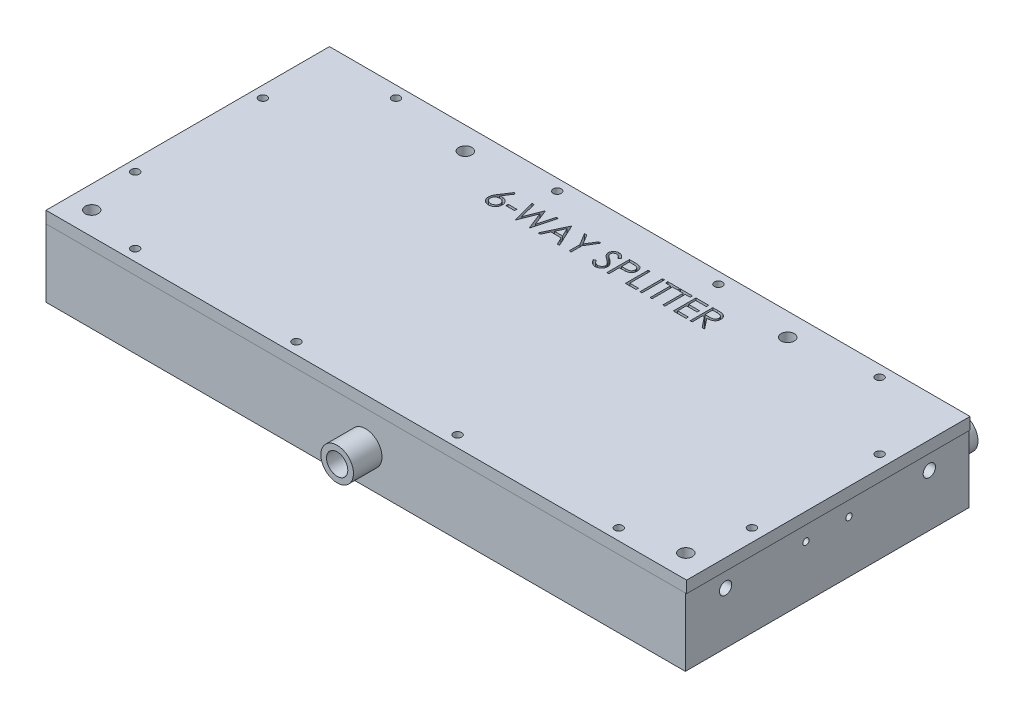
SolidWorks part; units mm, degrees
ref_plane "Front" through (0, 0, 0) normal (0, 0, 1) x (1, 0, 0)
ref_plane "Top" through (0, 0, 0) normal (0, 1, 0) x (1, 0, 0)
ref_plane "Right" through (0, 0, 0) normal (1, 0, 0) x (0, 0, -1)
sketch "Sketch1" plane through (0, 0, 0) normal (0, 1, 0) x (1, 0, 0)
  line L1 (0, 0) -> (179.324, 0)
  line L2 (0, 0) -> (0, 79.502)
  line L3 (0, 79.502) -> (179.324, 79.502)
  line L4 (179.324, 0) -> (179.324, 79.502)
  dimension "D1" = 79.502
  dimension "D2" = 179.324
extrude "Extrude-Thin1" add sketch "Sketch1" along normal blind 19.05 thin thin type one direction reverse wall 6.35
sketch "Sketch10" plane through (0, 0, 0) normal (0, -1, 0) x (1, 0, 0)
  line L0 (0, 0) -> (0, -79.502)
  line L1 (0, 0) -> (179.324, 0)
  line L2 (0, -79.502) -> (179.324, -79.502)
  line L3 (179.324, 0) -> (179.324, -79.502)
  line L4 (163.4056, -15.457) -> (144.9314, -15.457) construction
  line L5 (163.4056, -23.0271) -> (144.9314, -23.0271)
  line L6 (163.4056, -7.8869) -> (144.9314, -7.8869)
  line L7 (123.2539, -15.457) -> (56.0701, -15.457) construction
  line L8 (123.2539, -23.0271) -> (56.0701, -23.0271)
  line L9 (123.2539, -7.8869) -> (56.0701, -7.8869)
  line L10 (89.662, 0) -> (89.662, -15.457) construction
  line L11 (179.324, 0) -> (179.324, -79.502) construction
  line L12 (33.8656, -15.457) -> (15.3914, -15.457) construction
  line L13 (33.8656, -23.0271) -> (15.3914, -23.0271)
  line L14 (33.8656, -7.8869) -> (15.3914, -7.8869)
  arc A0 (163.4056, -23.0271) -> (163.4056, -7.8869) centre (163.4056, -15.457) ccw
  arc A1 (144.9314, -7.8869) -> (144.9314, -23.0271) centre (144.9314, -15.457) ccw
  arc A2 (123.2539, -23.0271) -> (123.2539, -7.8869) centre (123.2539, -15.457) ccw
  arc A3 (56.0701, -7.8869) -> (56.0701, -23.0271) centre (56.0701, -15.457) ccw
  arc A4 (33.8656, -23.0271) -> (33.8656, -7.8869) centre (33.8656, -15.457) ccw
  arc A5 (15.3914, -7.8869) -> (15.3914, -23.0271) centre (15.3914, -15.457) ccw
  point P8 (154.1685, -15.457)
  point P15 (89.662, -15.457)
  point P29 (24.6285, -15.457)
extrude "Boss-Extrude1" add sketch "Sketch10" against normal blind 5.715
sketch "Sketch11" plane through (0, 19.05, 0) normal (0, 1, 0) x (1, 0, 0)
  line L0 (0, 0) -> (0, 79.502)
  line L1 (0, 0) -> (179.6701, 0)
  line L2 (0, 79.502) -> (179.6701, 79.502)
  line L3 (179.6701, 0) -> (179.6701, 79.502)
extrude "Boss-Extrude2" add sketch "Sketch11" along normal blind 3.302 separate body
hole_wizard "#6 Clearance Hole1" positions "Sketch2" profile "Sketch3" hole size "#6" standard "ANSI Inch" end condition through all
sketch "Sketch2" plane through (0, 22.352, 0) normal (0, 1, 0) x (1, 0, 0)
  line L0 (0, 79.502) -> (0, 0) construction
  line L1 (179.324, 79.502) -> (0, 79.502) construction
  line L3 (44.45, 73.152) -> (134.874, 73.152) construction
  line L5 (6.35, 6.477) -> (172.974, 6.477) construction
  point P0 (44.45, 73.152)
  point P2 (134.874, 73.152)
  point P4 (172.974, 6.477)
  point P6 (6.35, 6.477)
  dimension "D1" = 44.45
  dimension "D2" = 6.35
  dimension "D3" = 134.874
  dimension "D4" = 172.974
  dimension "D5" = 6.35
  dimension "D6" = 73.025
sketch "Sketch3" plane through (44.45, 22.352, -73.152) normal (1, 0, 0) x (0, 0, 1)
  line L0 (0, 0) -> (0, 22.352)
  line L1 (0, 22.352) -> (1.8288, 22.352)
  line L2 (1.8288, 22.352) -> (1.8288, 0)
  line L5 (1.8288, 0) -> (0, 0)
  line L11 (0, -6.35) -> (0, 107.95) construction
  dimension "Thru Hole Dia." = 3.6576
  dimension "Thru Hole Depth" = 22.352
sketch "Sketch4" plane through (0, 0, 0) normal (0, 0, 1) x (1, 0, 0)
  line L0 (89.662, 19.05) -> (89.662, 9.525) construction
  line L1 (0, 19.05) -> (179.324, 19.05) construction
  line L2 (89.662, 9.525) -> (0, 9.525) construction
  line L3 (0, 19.05) -> (0, 0) construction
  circle A0 centre (89.662, 9.525) radius 4.572
  dimension "D1" = 9.144
extrude "Extrude-Thin2" add sketch "Sketch4" along normal blind 8.001 thin thin type one direction reverse wall 1.5875
sketch "Sketch5" plane through (0, 0, -79.502) normal (0, 0, -1) x (-1, 0, 0)
  line L0 (-89.662, 19.05) -> (-89.662, 9.525) construction
  line L1 (-179.324, 19.05) -> (0, 19.05) construction
  line L2 (-179.324, 9.525) -> (0, 9.525) construction
  line L3 (0, 19.05) -> (0, 0) construction
  line L4 (-10, 9.525) -> (-32.606, 9.525) construction
  line L6 (-169.324, 9.525) -> (-146.718, 9.525) construction
  circle A0 centre (-10, 9.525) radius 4.572
  circle A1 centre (-32.606, 9.525) radius 4.572
  circle A2 centre (-55.212, 9.525) radius 4.572
  circle A3 centre (-124.112, 9.525) radius 4.572
  circle A7 centre (-146.718, 9.525) radius 4.572
  circle A8 centre (-169.324, 9.525) radius 4.572
  dimension "D1" = 9.144
  dimension "D3" = 22.606
  dimension "D4" = 10
  dimension "D2" = 3
extrude "Extrude-Thin3" add sketch "Sketch5" along normal blind 8.001 thin thin type one direction reverse wall 1.5875
hole_wizard "#4-40 Tapped Hole1" positions "Sketch6" profile "Sketch7" tap size "#4-40" standard "ANSI Inch" end condition through all
sketch "Sketch6" plane through (0, 22.352, 0) normal (0, 1, 0) x (1, 0, 0)
  line L0 (0, 79.502) -> (0, 0) construction
  line L1 (21.844, 3.175) -> (67.056, 3.175) construction
  line L2 (67.056, 3.175) -> (112.268, 3.175) construction
  line L3 (112.268, 3.175) -> (157.48, 3.175) construction
  line L4 (157.48, 3.175) -> (157.48, 76.327) construction
  line L5 (157.48, 76.327) -> (112.268, 76.327) construction
  line L6 (112.268, 76.327) -> (67.056, 76.327) construction
  line L7 (67.056, 76.327) -> (21.844, 76.327) construction
  line L8 (21.844, 76.327) -> (21.844, 3.175) construction
  line L10 (0, 0) -> (179.324, 0) construction
  line L11 (179.324, 79.502) -> (0, 79.502) construction
  line L12 (112.268, 3.175) -> (112.268, 76.327) construction
  line L14 (67.056, 3.175) -> (67.056, 76.327) construction
  line L16 (176.149, 21.844) -> (176.149, 57.658) construction
  line L18 (176.149, 57.658) -> (3.175, 57.658) construction
  line L19 (3.175, 57.658) -> (3.175, 21.844) construction
  line L20 (3.175, 21.844) -> (176.149, 21.844) construction
  line L26 (179.324, 0) -> (179.324, 79.502) construction
  line L27 (44.45, 76.327) -> (44.45, 73.152) construction
  point P0 (157.48, 76.327)
  point P2 (112.268, 76.327)
  point P4 (67.056, 76.327)
  point P6 (21.844, 76.327)
  point P8 (21.844, 3.175)
  point P10 (67.056, 3.175)
  point P12 (112.268, 3.175)
  point P14 (157.48, 3.175)
  point P16 (176.149, 21.844)
  point P18 (176.149, 57.658)
  point P20 (3.175, 57.658)
  point P22 (3.175, 21.844)
  point P62 (89.662, 3.175)
  point P78 (3.175, 39.751)
  dimension "D1" = 21.844
  dimension "D2" = 3.175
  dimension "D3" = 3.175
  dimension "D4" = 89.662
  dimension "D5" = 39.751
  dimension "D6" = 21.844
  dimension "D7" = 3.175
  dimension "D8" = 3.175
sketch "Sketch7" plane through (157.48, 22.352, -76.327) normal (1, 0, 0) x (0, 0, 1)
  line L0 (0, 0) -> (0, 22.352)
  line L1 (0, 22.352) -> (1.1303, 22.352)
  line L2 (1.1303, 22.352) -> (1.1303, 0)
  line L5 (1.1303, 0) -> (0, 0)
  line L11 (0, -6.35) -> (0, 107.95) construction
  dimension "Thru Tap Drill Dia." = 2.2606
  dimension "Thru Tap Drill Depth" = 22.352
cosmetic thread "Hole Thread13" parameters "D2"=2.8448
cosmetic thread "Hole Thread14" parameters "D2"=2.8448
cosmetic thread "Hole Thread15" parameters "D2"=2.8448
cosmetic thread "Hole Thread16" parameters "D2"=2.8448
cosmetic thread "Hole Thread17" parameters "D2"=2.8448
cosmetic thread "Hole Thread18" parameters "D2"=2.8448
cosmetic thread "Hole Thread19" parameters "D2"=2.8448
cosmetic thread "Hole Thread20" parameters "D2"=2.8448
cosmetic thread "Hole Thread21" parameters "D2"=2.8448
cosmetic thread "Hole Thread22" parameters "D2"=2.8448
cosmetic thread "Hole Thread23" parameters "D2"=2.8448
cosmetic thread "Hole Thread24" parameters "D2"=2.8448
sketch "Sketch8" plane through (0, 22.352, 0) normal (0, 1, 0) x (1, 0, 0)
  text T0 "  6-WAY SPLITTER" font "Century Gothic" height 6.35
extrude "Cut-Extrude1" cut sketch "Sketch8" against normal through all both
sketch "Sketch9" plane through (0, 0, -79.502) normal (0, 0, -1) x (-1, 0, 0)
  text T0 "a                b                c                                                      d                e                 f                  "
extrude "Cut-Extrude2" cut sketch "Sketch9" against normal blind 2.54
hole_wizard "#8-32 Tapped Hole1" positions "Sketch12" profile "Sketch13" tap size "#8-32" standard "ANSI Inch"
sketch "Sketch12" plane through (0, 0, 0) normal (-1, 0, 0) x (0, 0, 1)
  line L0 (-68.2244, 14.605) -> (-11.0744, 14.605) construction
  line L2 (-68.2244, 14.605) -> (-68.2244, 19.05) construction
  line L3 (-79.502, 19.05) -> (0, 19.05) construction
  line L5 (-79.502, 19.05) -> (-79.502, 0) construction
  point P0 (-11.0744, 14.605)
  point P2 (-68.2244, 14.605)
  dimension "D1" = 4.445
  dimension "D2" = 11.2776
  dimension "D3" = 57.15
cosmetic thread "Hole Thread25" parameters "D1"=8.3312, "D2"=4.1656
cosmetic thread "Hole Thread26" parameters "D1"=8.3312, "D2"=4.1656
sketch "Sketch13" plane through (0, 14.605, -11.0744) normal (0, 1, 0) x (0, 0, 1)
  line L0 (0, 0) -> (0, 13.3314)
  line L1 (0, 13.3314) -> (1.7272, 12.2936)
  line L2 (1.7272, 12.2936) -> (1.7272, 0)
  line L5 (1.7272, 0) -> (0, 0)
  line L10 (0, 13.3314) -> (-1.7272, 12.2936) construction
  line L11 (0, -6.35) -> (0, 107.95) construction
  dimension "Tap Drill Dia." = 3.4544
  dimension "Tap Drill Depth" = 12.2936
  dimension "Drill Angle" = 118
hole_wizard "#8-32 Tapped Hole2" positions "Sketch14" profile "Sketch15" tap size "#8-32" standard "ANSI Inch"
sketch "Sketch14" plane through (179.324, 0, 0) normal (1, 0, 0) x (0, 0, -1)
  line L0 (11.2776, 14.605) -> (68.4276, 14.605) construction
  line L2 (11.2776, 14.605) -> (11.2776, 19.05) construction
  line L3 (0, 19.05) -> (79.502, 19.05) construction
  line L5 (0, 19.05) -> (0, 0) construction
  point P0 (11.2776, 14.605)
  point P2 (68.4276, 14.605)
  dimension "D1" = 4.445
  dimension "D3" = 57.15
  dimension "D2" = 11.2776
sketch "Sketch15" plane through (179.324, 14.605, -11.2776) normal (0, 1, 0) x (0, 0, -1)
  line L0 (0, 0) -> (0, 13.3314)
  line L1 (0, 13.3314) -> (1.7272, 12.2936)
  line L2 (1.7272, 12.2936) -> (1.7272, 0)
  line L5 (1.7272, 0) -> (0, 0)
  line L10 (0, 13.3314) -> (-1.7272, 12.2936) construction
  line L11 (0, -6.35) -> (0, 107.95) construction
  dimension "Tap Drill Dia." = 3.4544
  dimension "Tap Drill Depth" = 12.2936
  dimension "Drill Angle" = 118
cosmetic thread "Hole Thread27" parameters "D1"=8.3312, "D2"=4.1656
cosmetic thread "Hole Thread28" parameters "D1"=8.3312, "D2"=4.1656
hole_wizard "#2-56 Tapped Hole1" positions "Sketch16" profile "Sketch17" tap size "#2-56" standard "ANSI Inch"
sketch "Sketch16" plane through (179.324, 0, 0) normal (1, 0, 0) x (0, 0, -1)
  line L1 (39.8526, 14.605) -> (33.8201, 14.605) construction
  line L3 (39.8526, 14.605) -> (45.8851, 14.605) construction
  line L5 (11.2776, 14.605) -> (68.4276, 14.605) construction
  point P6 (33.8201, 14.605)
  point P8 (45.8851, 14.605)
  point P25 (39.8526, 14.605)
  dimension "D1" = 12.065
sketch "Sketch17" plane through (179.324, 14.605, -33.8201) normal (0, 1, 0) x (0, 0, -1)
  line L0 (0, 0) -> (0, 6.2746)
  line L1 (0, 6.2746) -> (0.889, 5.7404)
  line L2 (0.889, 5.7404) -> (0.889, 0)
  line L5 (0.889, 0) -> (0, 0)
  line L10 (0, 6.2746) -> (-0.889, 5.7404) construction
  line L11 (0, -6.35) -> (0, 107.95) construction
  dimension "Tap Drill Dia." = 1.778
  dimension "Tap Drill Depth" = 5.7404
  dimension "Drill Angle" = 118
cosmetic thread "Hole Thread29" parameters "D1"=4.3688, "D2"=2.1844
cosmetic thread "Hole Thread30" parameters "D1"=4.3688, "D2"=2.1844
equation "\"D7@Sketch6\"=\"D2@Sketch6\""
equation "\"D3@Sketch6\"=\"D2@Sketch6\""
equation "\"D8@Sketch6\"=\"D2@Sketch6\""
equation "\"D6@Sketch6\"=\"D1@Sketch6\""
equation "\"D3@Sketch12\"=3.138-\"D2@Sketch12\"*2"
equation "\"D3@Sketch14\"=3.138-2*\"D2@Sketch14\""
